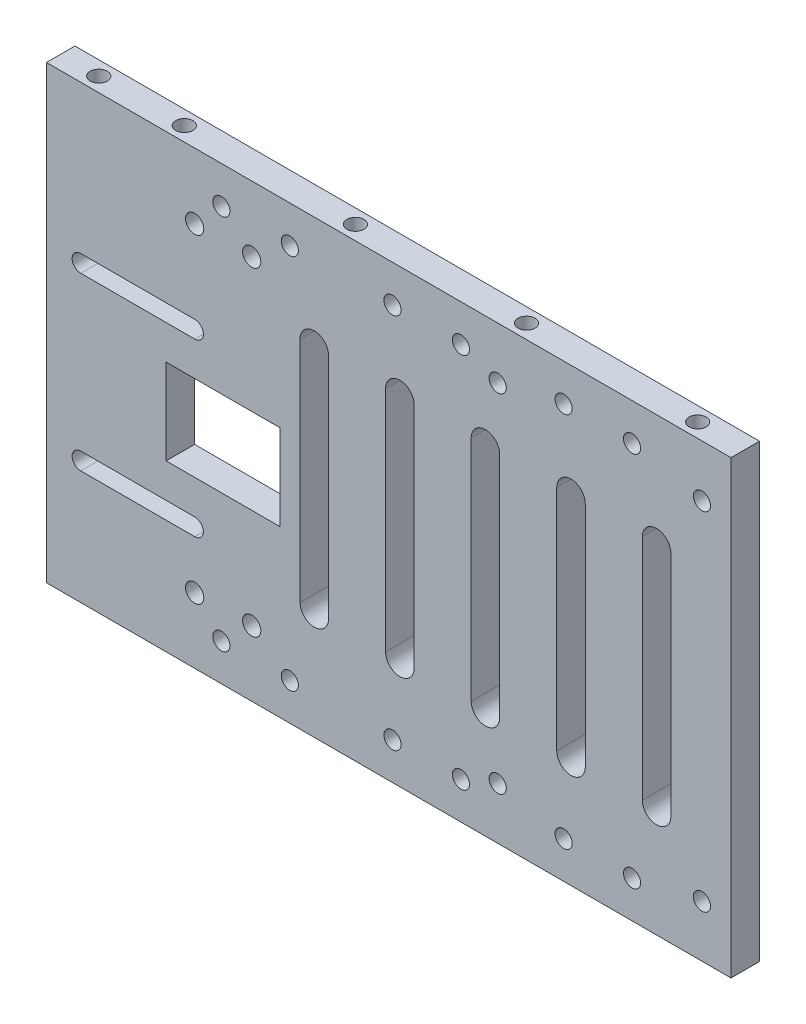
SolidWorks part; units mm, degrees
ref_plane "前视基准面" through (0, 0, 0) normal (0, 0, 1) x (1, 0, 0)
ref_plane "上视基准面" through (0, 0, 0) normal (0, 1, 0) x (1, 0, 0)
ref_plane "右视基准面" through (0, 0, 0) normal (1, 0, 0) x (0, 0, -1)
other "Configuration Table"
sketch "草图1" plane through (0, 0, 0) normal (0, 0, 1) x (1, 0, 0)
  line L1 (-60, -39.5) -> (60, -39.5)
  line L2 (-60, -39.5) -> (-60, 39.5)
  line L3 (-60, 39.5) -> (60, 39.5)
  line L4 (60, -39.5) -> (60, 39.5)
  line L5 (-60, -39.5) -> (60, 39.5) construction
  line L6 (-60, 39.5) -> (60, -39.5) construction
  point P0 (0, 0)
  dimension "D1" = 79
  dimension "D2" = 120
extrude "凸台-拉伸1" add sketch "草图1" along normal blind 5
sketch "草图2" plane through (0, 0, 0) normal (0, 0, -1) x (-1, 0, 0)
  circle A0 centre (-42.656, -33) radius 3.1
  circle A1 centre (-30.656, -33) radius 3.1
extrude "切除-拉伸1" cut sketch "草图2" against normal blind 2
sketch "草图3" plane through (0, 0, 2) normal (0, 0, -1) x (-1, 0, 0)
  circle A0 centre (-42.656, -33) radius 1.5
  circle A1 centre (-30.656, -33) radius 1.5
extrude "切除-拉伸2" cut sketch "草图3" against normal through all
pattern_linear "阵列(线性)1" count 3 spacing 30 along (-1, 0, 0) of "切除-拉伸1", "切除-拉伸2"
mirror "镜向2" about plane through (0, 0, 0) normal (0, 1, 0) of "阵列(线性)1"
sketch "草图4" plane through (0, 0, 0) normal (0, 0, -1) x (-1, 0, 0)
  line L0 (34, 12) -> (54, 12) construction
  line L1 (34, 15.1) -> (54, 15.1)
  line L2 (34, 8.9) -> (54, 8.9)
  line L3 (60, 39.5) -> (60, -39.5) construction
  line L4 (34.3421, -4) -> (54.815, -4) construction
  line L5 (34.3421, 17) -> (34.3421, -25) construction
  line L6 (54.815, 17) -> (54.815, -6) construction
  line L7 (34, -20) -> (54, -20) construction
  line L8 (34, -23.1) -> (54, -23.1)
  line L9 (34, -16.9) -> (54, -16.9)
  arc A4 (34, 15.1) -> (34, 8.9) centre (34, 12) ccw
  arc A5 (54, 8.9) -> (54, 15.1) centre (54, 12) ccw
  arc A6 (34, -23.1) -> (34, -16.9) centre (34, -20) cw
  arc A7 (54, -16.9) -> (54, -23.1) centre (54, -20) cw
  point P8 (44, 12)
  point P17 (44, -20)
  dimension "D1" = 20
  dimension "D2" = 6
extrude "切除-拉伸3" cut sketch "草图4" against normal blind 1.5
sketch "草图5" plane through (0, 0, 1.5) normal (0, 0, -1) x (-1, 0, 0)
  line L0 (54, 12) -> (34, 12) construction
  line L1 (54, 10.5) -> (34, 10.5)
  line L2 (54, 13.5) -> (34, 13.5)
  line L3 (60, 39.5) -> (60, -39.5) construction
  line L4 (34.3421, -3) -> (54.815, -3) construction
  line L5 (54.815, 17) -> (54.815, -6) construction
  line L6 (54, -18) -> (34, -18) construction
  line L7 (54, -16.5) -> (34, -16.5)
  line L8 (54, -19.5) -> (34, -19.5)
  arc A0 (54, 10.5) -> (54, 13.5) centre (54, 12) ccw
  arc A1 (34, 13.5) -> (34, 10.5) centre (34, 12) ccw
  arc A2 (54, -16.5) -> (54, -19.5) centre (54, -18) cw
  arc A3 (34, -19.5) -> (34, -16.5) centre (34, -18) cw
  point P4 (44, 12)
  point P18 (44, -18)
  dimension "D1" = 20
  dimension "D2" = 6
extrude "切除-拉伸4" cut sketch "草图5" against normal through all
sketch "草图7" plane through (0, -39.5, 0) normal (0, -1, 0) x (1, 0, 0)
  line L0 (46.656, 31) -> (46.656, 5) construction
  circle A0 centre (51.656, 2.5) radius 1.5
  circle A1 centre (21.656, 2.5) radius 1.5
  circle A2 centre (-8.344, 2.5) radius 1.5
  circle A3 centre (-38.344, 2.5) radius 1.5
  circle A4 centre (-53.344, 2.5) radius 1.5
  dimension "D1" = 5
  dimension "D2" = 15
extrude "切除-拉伸6" cut sketch "草图7" against normal blind 5
mirror "镜向3" about plane through (0, 0, 0) normal (0, 1, 0) of "切除-拉伸6"
sketch "草图9" plane through (0, 0, 0) normal (0, 0, -1) x (-1, 0, 0)
  line L0 (-46.9526, -20.2662) -> (-46.9526, 19.7338) construction
  line L1 (-49.4526, -20.2662) -> (-49.4526, 19.7338)
  line L2 (-44.4526, -20.2662) -> (-44.4526, 19.7338)
  line L3 (-31.9526, -20.2662) -> (-31.9526, 19.7338) construction
  line L4 (-34.4526, -20.2662) -> (-34.4526, 19.7338)
  line L5 (-29.4526, -20.2662) -> (-29.4526, 19.7338)
  line L6 (-16.9526, -20.2662) -> (-16.9526, 19.7338) construction
  line L7 (-19.4526, -20.2662) -> (-19.4526, 19.7338)
  line L8 (-14.4526, -20.2662) -> (-14.4526, 19.7338)
  line L9 (-1.9526, -20.2662) -> (-1.9526, 19.7338) construction
  line L10 (-4.4526, -20.2662) -> (-4.4526, 19.7338)
  line L11 (0.5474, -20.2662) -> (0.5474, 19.7338)
  line L12 (13.0474, -20.2662) -> (13.0474, 19.7338) construction
  line L13 (10.5474, -20.2662) -> (10.5474, 19.7338)
  line L14 (15.5474, -20.2662) -> (15.5474, 19.7338)
  circle A0 centre (24.0277, -28) radius 1.6 construction
  circle A1 centre (34.0277, -28) radius 1.6 construction
  circle A2 centre (24.0277, 28) radius 1.6 construction
  circle A3 centre (34.0277, 28) radius 1.6 construction
  circle A4 centre (24.0277, -28) radius 1.6
  circle A5 centre (34.0277, -28) radius 1.6
  circle A6 centre (24.0277, 28) radius 1.6
  circle A7 centre (34.0277, 28) radius 1.6
  arc A8 (-49.4526, -20.2662) -> (-44.4526, -20.2662) centre (-46.9526, -20.2662) ccw
  arc A9 (-44.4526, 19.7338) -> (-49.4526, 19.7338) centre (-46.9526, 19.7338) ccw
  arc A10 (-34.4526, -20.2662) -> (-29.4526, -20.2662) centre (-31.9526, -20.2662) ccw
  arc A11 (-29.4526, 19.7338) -> (-34.4526, 19.7338) centre (-31.9526, 19.7338) ccw
  circle A16 centre (-19.1038, 30.4) radius 1.5
  circle A17 centre (-54.9038, 30.4) radius 1.5
  circle A18 centre (-19.1038, -30.4) radius 1.5
  circle A19 centre (-54.9038, -30.4) radius 1.5
  arc A20 (-19.4526, -20.2662) -> (-14.4526, -20.2662) centre (-16.9526, -20.2662) ccw
  arc A21 (-14.4526, 19.7338) -> (-19.4526, 19.7338) centre (-16.9526, 19.7338) ccw
  arc A22 (-4.4526, -20.2662) -> (0.5474, -20.2662) centre (-1.9526, -20.2662) ccw
  arc A23 (0.5474, 19.7338) -> (-4.4526, 19.7338) centre (-1.9526, 19.7338) ccw
  arc A24 (10.5474, -20.2662) -> (15.5474, -20.2662) centre (13.0474, -20.2662) ccw
  arc A25 (15.5474, 19.7338) -> (10.5474, 19.7338) centre (13.0474, 19.7338) ccw
  point P17 (-46.9526, -0.2662)
  point P31 (-31.9526, -0.2662)
  point P38 (-16.9526, -0.2662)
  point P45 (-1.9526, -0.2662)
  point P52 (13.0474, -0.2662)
  dimension "D1" = 5
extrude "切除-拉伸7" cut sketch "草图9" against normal through all
sketch "草图11" plane through (0, 0, 5) normal (0, 0, 1) x (1, 0, 0)
  line L0 (-29.0277, 4.5) -> (-29.0277, -10.5)
  line L4 (-39.0277, -10.5) -> (-19.0277, -10.5)
  line L5 (-19.0277, -10.5) -> (-19.0277, 4.5)
  line L6 (-19.0277, 4.5) -> (-39.0277, 4.5)
  line L7 (-39.0277, 4.5) -> (-39.0277, -10.5)
  line L8 (-39.0277, -10.5) -> (-19.0277, -10.5)
  line L9 (-19.0277, -10.5) -> (-19.0277, 4.5)
  line L10 (-19.0277, 4.5) -> (-39.0277, 4.5)
  line L11 (-39.0277, 4.5) -> (-39.0277, -10.5)
  dimension "D1" = 0
extrude "切除-拉伸8" cut sketch "草图11" against normal through all contours L9 L10 L0 L8 | L10 L11 L8 L0 region at (-24.0277, -3, 5) region at (-34.0277, -3, 5)
